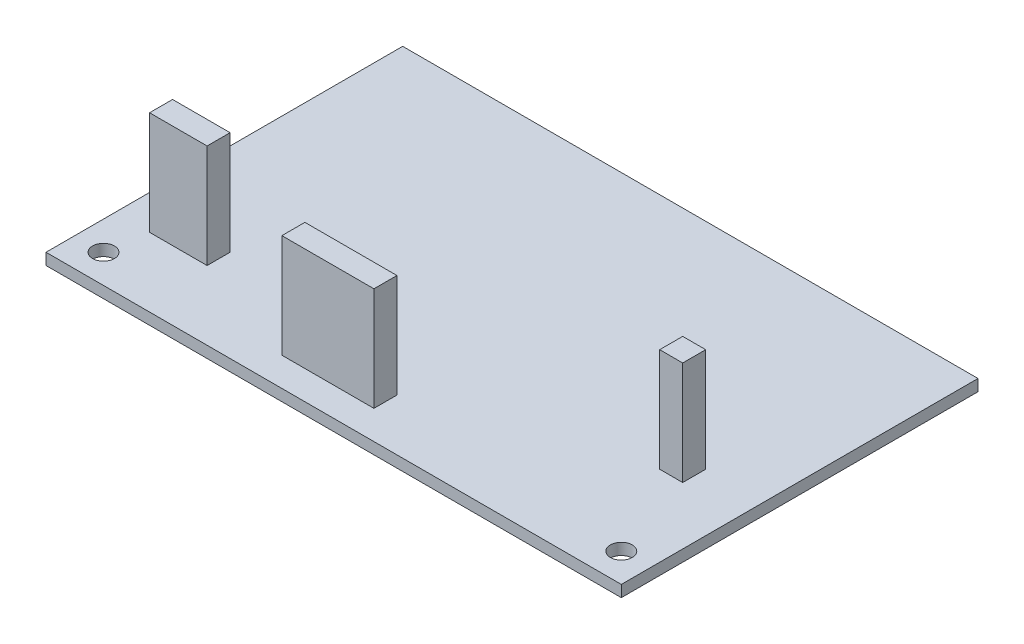
SolidWorks part; units mm, degrees
ref_plane "Plan de face" through (0, 0, 0) normal (0, 0, 1) x (1, 0, 0)
ref_plane "Plan de dessus" through (0, 0, 0) normal (0, 1, 0) x (1, 0, 0)
ref_plane "Plan de droite" through (0, 0, 0) normal (1, 0, 0) x (0, 0, -1)
sketch "Esquisse1" plane through (0, 0, 0) normal (0, 1, 0) x (1, 0, 0)
  line L1 (-22.4796, 10.3787) -> (27.5204, 10.3787)
  line L2 (-22.4796, 10.3787) -> (-22.4796, -20.6213)
  line L3 (-22.4796, -20.6213) -> (27.5204, -20.6213)
  line L4 (27.5204, 10.3787) -> (27.5204, -20.6213)
  line L5 (-19.4796, -12.6213) -> (-14.4796, -12.6213)
  line L6 (-19.4796, -12.6213) -> (-19.4796, -14.6213)
  line L7 (-19.4796, -14.6213) -> (-14.4796, -14.6213)
  line L8 (-14.4796, -12.6213) -> (-14.4796, -14.6213)
  line L9 (-4.4796, -16.1213) -> (3.5204, -16.1213)
  line L10 (-4.4796, -16.1213) -> (-4.4796, -18.1213)
  line L11 (-4.4796, -18.1213) -> (3.5204, -18.1213)
  line L12 (3.5204, -16.1213) -> (3.5204, -18.1213)
  line L13 (20.5204, -8.2861) -> (22.5204, -8.2861)
  line L14 (20.5204, -8.2861) -> (20.5204, -10.2861)
  line L15 (20.5204, -10.2861) -> (22.5204, -10.2861)
  line L16 (22.5204, -8.2861) -> (22.5204, -10.2861)
  circle A0 centre (-19.9796, -18.1213) radius 0.95
  circle A1 centre (25.0204, -18.1213) radius 0.95
  dimension "D3" = 2.5
  dimension "D1" = 50
  dimension "D2" = 31
  dimension "D4" = 2.5
  dimension "D5" = 2.5
  dimension "D6" = 23
  dimension "D7" = 25
  dimension "D8" = 3
  dimension "D9" = 8
  dimension "D10" = 18
  dimension "D11" = 26
  dimension "D12" = 2
  dimension "D13" = 5
  dimension "D14" = 7
  dimension "D15" = 2
extrude "Boss.-Extru.7" add sketch "Esquisse1" along normal blind 9 and the other way blind 1 contours L12 L9 L10 L11 region at (-0.4796, 0, 17.1213)
extrude "Boss.-Extru.8" add sketch "Esquisse1<10>" along normal blind 9 and the other way blind 1 separate body contours L8 L5 L6 L7 region at (-16.9796, 0, 13.6213)
sketch "Esquisse1<10>" plane through (0, 0, 0) normal (0, 1, 0) x (1, 0, 0) same geometry as "Esquisse1"
extrude "Boss.-Extru.9" add sketch "Esquisse1<11>" along normal blind 9 and the other way blind 1 separate body contours L16 L13 L14 L15 region at (21.5204, 0, 9.2861)
sketch "Esquisse1<11>" plane through (0, 0, 0) normal (0, 1, 0) x (1, 0, 0) same geometry as "Esquisse1"
extrude "Boss.-Extru.10" add sketch "Esquisse1<12>" against normal blind 1
sketch "Esquisse1<12>" plane through (0, 0, 0) normal (0, 1, 0) x (1, 0, 0) same geometry as "Esquisse1"
